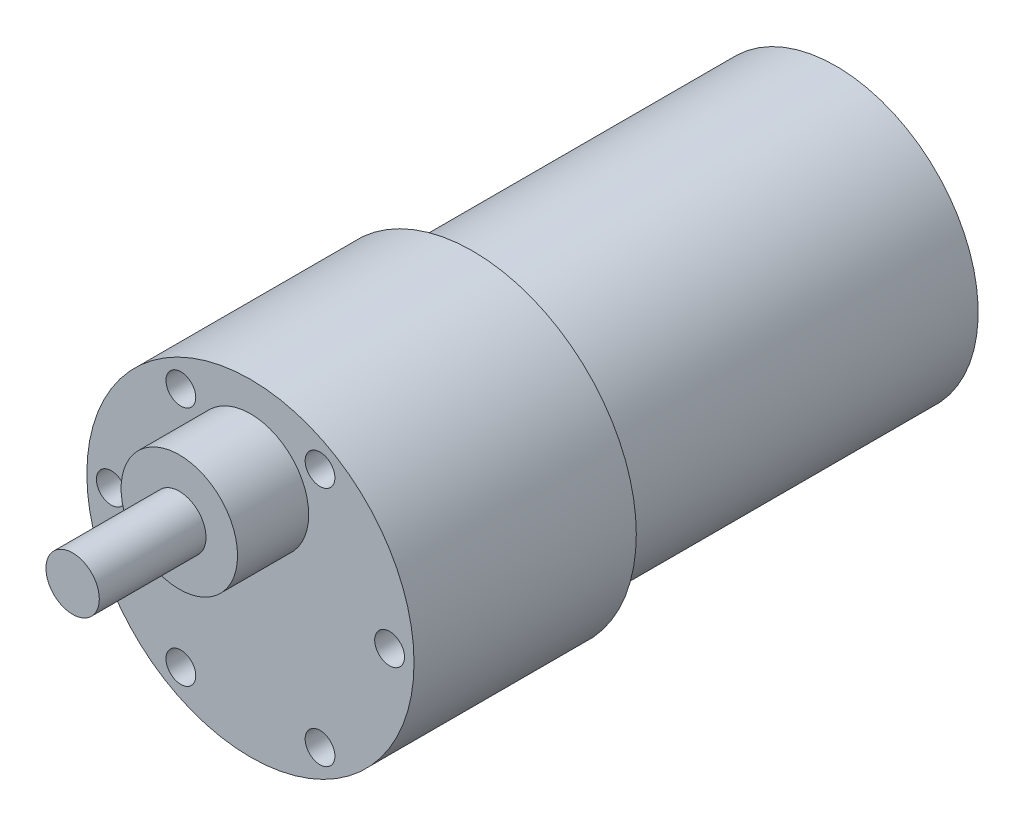
SolidWorks part; units mm, degrees
ref_plane "Front Plane" through (0, 0, 0) normal (0, 0, 1) x (1, 0, 0)
ref_plane "Top Plane" through (0, 0, 0) normal (0, 1, 0) x (1, 0, 0)
ref_plane "Right Plane" through (0, 0, 0) normal (1, 0, 0) x (0, 0, -1)
sketch "Sketch1" plane through (0, 0, 0) normal (0, 0, 1) x (1, 0, 0)
  circle A0 centre (0, 0) radius 18.4
  dimension "D1" = 36.8
extrude "Boss-Extrude1" add sketch "Sketch1" against normal blind 25
sketch "Sketch2" plane through (0, 0, -25) normal (0, 0, -1) x (-1, 0, 0)
  circle A0 centre (0, 0) radius 16
  dimension "D1" = 32
extrude "Boss-Extrude2" add sketch "Sketch2" along normal blind 40.85
sketch "Sketch3" plane through (0, 0, 0) normal (0, 0, 1) x (1, 0, 0)
  circle A0 centre (15.65, 0) radius 1.675
  circle A1 centre (7.825, -13.5533) radius 1.675
  circle A2 centre (-7.825, -13.5533) radius 1.675
  circle A3 centre (-15.65, 0) radius 1.675
  circle A4 centre (-7.825, 13.5533) radius 1.675
  circle A5 centre (7.825, 13.5533) radius 1.675
  point P15 (0, 0)
  dimension "D1" = 3.35
  dimension "D2" = 15.65
  dimension "D3" = 6
extrude "Cut-Extrude1" cut sketch "Sketch3" against normal blind 10
sketch "Sketch4" plane through (0, 0, 0) normal (0, 0, 1) x (1, 0, 0)
  circle A0 centre (0, 8.5) radius 6.55
  dimension "D2" = 13.1
  dimension "D1" = 8.5
extrude "Boss-Extrude3" add sketch "Sketch4" along normal blind 8
sketch "Sketch5" plane through (0, 0, 8) normal (0, 0, 1) x (1, 0, 0)
  circle A0 centre (0, 8.5) radius 3
  dimension "D1" = 6
extrude "Boss-Extrude4" add sketch "Sketch5" along normal blind 12
